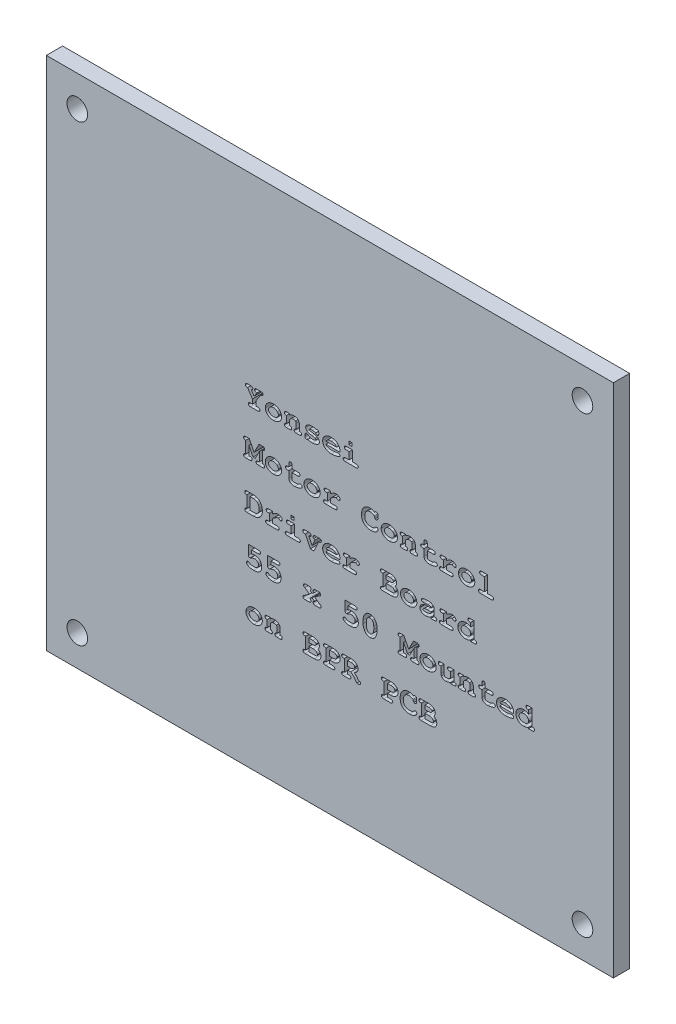
SolidWorks part; units mm, degrees
ref_plane "Front Plane" through (0, 0, 0) normal (0, 0, 1) x (1, 0, 0)
ref_plane "Top Plane" through (0, 0, 0) normal (0, 1, 0) x (1, 0, 0)
ref_plane "Right Plane" through (0, 0, 0) normal (1, 0, 0) x (0, 0, -1)
sketch "Sketch1" plane through (0, 0, 0) normal (0, 0, 1) x (1, 0, 0)
  line L1 (0, 0) -> (55, 0)
  line L2 (0, 0) -> (0, 50)
  line L3 (0, 50) -> (55, 50)
  line L4 (55, 0) -> (55, 50)
  dimension "D1" = 50
  dimension "D2" = 55
extrude "Boss-Extrude1" add sketch "Sketch1" along normal blind 1.575
sketch "Sketch2" plane through (0, 0, 1.575) normal (0, 0, 1) x (1, 0, 0)
  text T0 "Yonsei\r\nMotor Control\r\nDriver Board\r\n55 x 50 Mounted\r\non BPR PCB" font "Courier New" height in points 8
extrude "Cut-Extrude1" cut sketch "Sketch2" against normal through all
sketch "Sketch4" plane through (0, 0, 1.575) normal (0, 0, 1) x (1, 0, 0)
  line L0 (52, 54.4791) -> (52, -1.4791) construction
  line L1 (3, 54.4791) -> (3, -1.4791) construction
  line L2 (-10.5844, 47) -> (60.5411, 47) construction
  line L3 (-3.4603, 3) -> (61.5752, 3) construction
  circle A0 centre (52, 47) radius 1
  circle A1 centre (52, 3) radius 1
  circle A2 centre (3, 3) radius 1
  circle A3 centre (3, 47) radius 1
  point P8 (52, 47)
  point P9 (3, 47)
  point P14 (3, 3)
  point P15 (52, 3)
  dimension "D1" = 3
  dimension "D7" = 2
  dimension "D8" = 2
  dimension "D9" = 2
  dimension "D10" = 2
  dimension "D2" = 3
  dimension "D3" = 3
  dimension "D4" = 3
  dimension "D5" = 3
  dimension "D6" = 3
extrude "Cut-Extrude2" cut sketch "Sketch4" against normal through all
